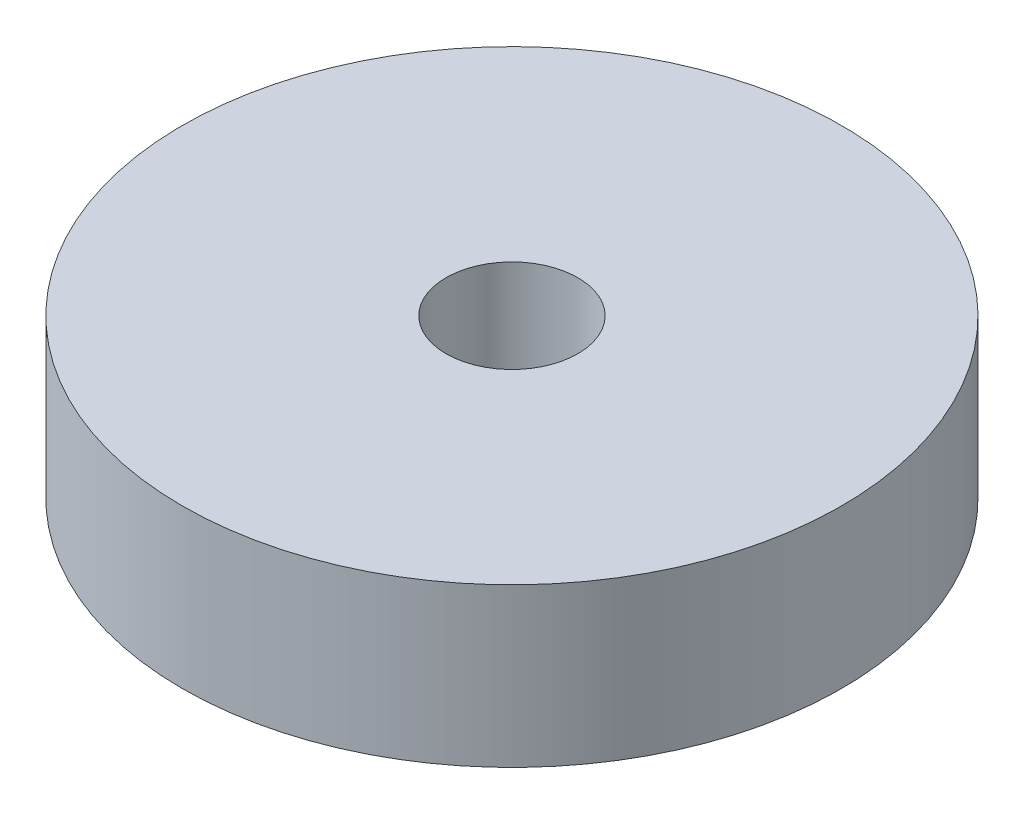
SolidWorks part; units mm, degrees
ref_plane "Front Plane" through (0, 0, 0) normal (0, 0, 1) x (1, 0, 0)
ref_plane "Top Plane" through (0, 0, 0) normal (0, 1, 0) x (1, 0, 0)
ref_plane "Right Plane" through (0, 0, 0) normal (1, 0, 0) x (0, 0, -1)
sketch "Sketch1" plane through (0, 0, 0) normal (0, 1, 0) x (1, 0, 0)
  circle A0 centre (0, 0) radius 37.5
  dimension "FLANGE_OD" = 75
extrude "Boss-Extrude1" add sketch "Sketch1" along normal blind 18
sketch "Sketch2" plane through (0, 0, 0) normal (0, 1, 0) x (1, 0, 0)
  circle A0 centre (0, 0) radius 7.5
  dimension "BORE_D" = 15
extrude "Cut-Extrude1" cut sketch "Sketch2" along normal through all
sketch "Sketch3" plane through (0, 18, 0) normal (0, 1, 0) x (1, 0, 0)
  circle A0 centre (0, 0) radius 5.3108 construction
  circle A1 centre (-5.3108, 0) radius 1.9397
  dimension "BOLT_D" = 3.8793
  dimension "BOLT_PCD" = 10.6216
extrude "Cut-Extrude2" cut sketch "Sketch3" against normal blind 17.7132 rebuild error yes
pattern_circular "CirPattern1" count 5 over 360 rebuild error yes
